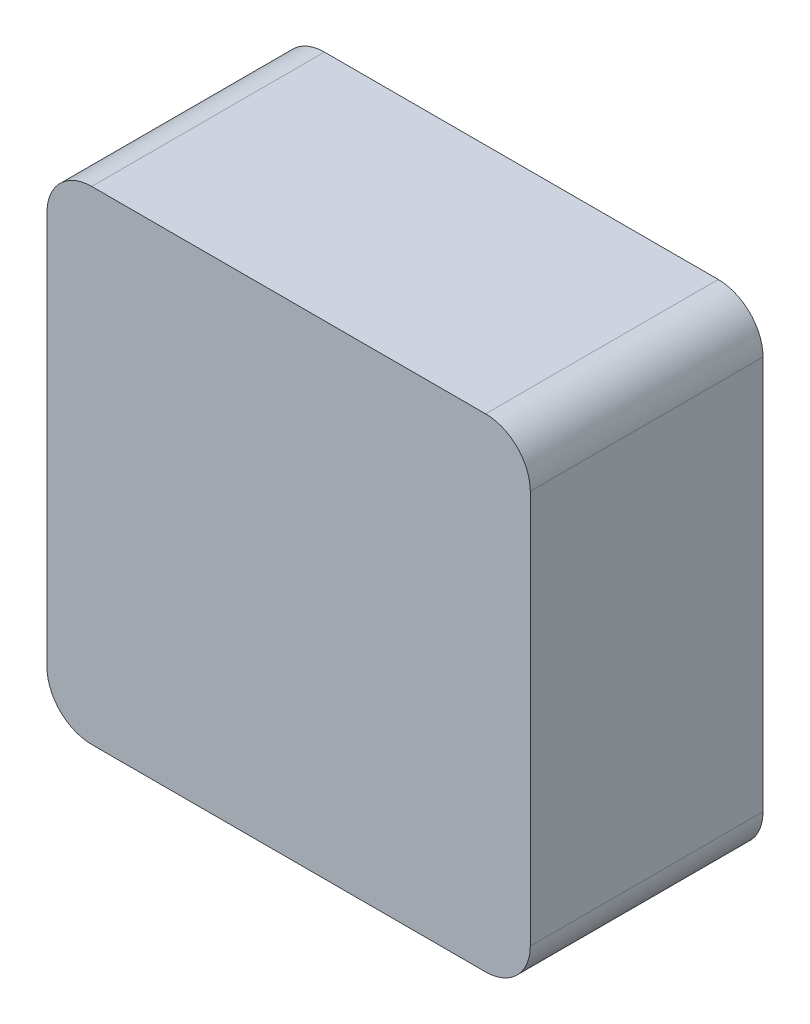
SolidWorks part; units mm, degrees
ref_plane "Alzado" through (0, 0, 0) normal (0, 0, 1) x (1, 0, 0)
ref_plane "Planta" through (0, 0, 0) normal (0, 1, 0) x (1, 0, 0)
ref_plane "Vista lateral" through (0, 0, 0) normal (1, 0, 0) x (0, 0, -1)
sketch "Croquis1" plane through (0, 0, 0) normal (0, 0, 1) x (1, 0, 0)
  line L1 (27, -27) -> (-27, -27)
  line L2 (27, -27) -> (27, 27)
  line L3 (27, 27) -> (-27, 27)
  line L4 (-27, -27) -> (-27, 27)
  line L5 (27, -27) -> (-27, 27) construction
  line L6 (27, 27) -> (-27, -27) construction
  point P0 (0, 0)
  dimension "D1" = 54
  dimension "D2" = 54
extrude "Saliente-Extruir1" add sketch "Croquis1" along normal blind 26
fillet "Redondeo1" radius 5 4 edges at (-27, -27, 13) (27, -27, 13) (27, 27, 13) (-27, 27, 13)
